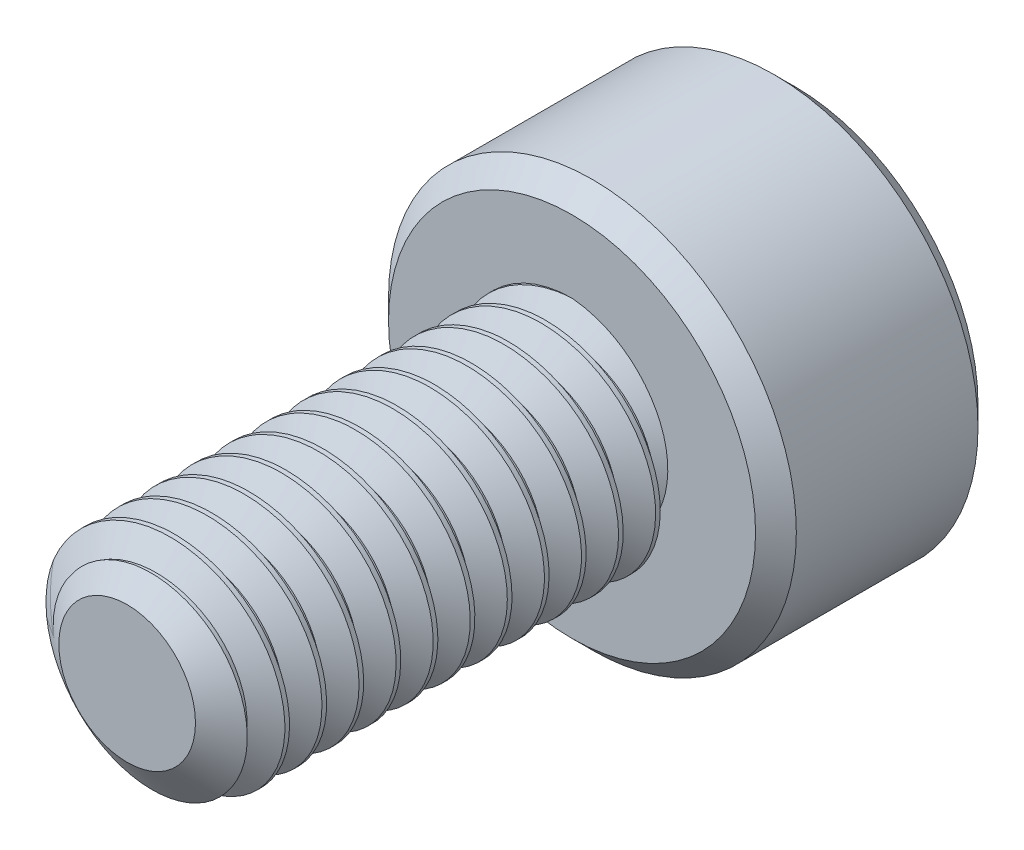
SolidWorks part; units mm, degrees
other "DetailItem1"
ref_plane "Front Plane" through (0, 0, 0) normal (0, 0, 1) x (1, 0, 0)
ref_plane "Top Plane" through (0, 0, 0) normal (0, 1, 0) x (1, 0, 0)
ref_plane "Right Plane" through (0, 0, 0) normal (1, 0, 0) x (0, 0, -1)
sketch "Sketch1" plane through (0, 0, 0) normal (0, 0, 1) x (1, 0, 0)
  circle A0 centre (0, 0) radius 1.5
  dimension "OD" = 3
extrude "Extrude1" add sketch "Sketch1" against normal blind 6
sketch "Sketch2" plane through (0, 0, 0) normal (0, 0, 1) x (1, 0, 0)
  circle A0 centre (0, 0) radius 1.5 construction
  circle A1 centre (0, 0) radius 1.5
curve "Helix/Spiral1" pitch 0.5 height 6.5 radius 1.5 centre (0, 0, 0) axis (0, 0, -1) start towards (0, 1, 0) parameters "pitch"=0.5
sketch "Sketch3" plane through (0, 0, 0) normal (1, 0, 0) x (0, 0, -1)
  line L0 (-0.4375, 1.5) -> (-0.25, 1.1752)
  line L1 (-0.25, 1.1752) -> (-0.1875, 1.1752)
  line L2 (-0.1875, 1.1752) -> (0, 1.5)
  line L3 (-0.4375, 1.5) -> (0, 1.5)
  line L4 (-0.2187, 1.5) -> (-0.2188, 1.1752) construction
  line L5 (-0.3438, 1.3376) -> (-0.0938, 1.3376) construction
  line L6 (0, 1.5) -> (0, -1.5) construction
  dimension "D1" = 0.0625
  dimension "D2" = 0.25
  dimension "D3" = 60
sweep "Cut-Sweep1" cut profiles "Sketch3" path "Helix/Spiral1" align with end faces yes
sketch "Sketch4" plane through (0, 0, 0) normal (1, 0, 0) x (0, 0, -1)
  line L0 (0.4053, 1.5) -> (0, 0.9212)
  line L1 (0, 0.9212) -> (0, 1.5)
  line L2 (0.4053, 1.5) -> (0, 1.5)
  line L3 (-0.4375, 1.5) -> (0, 1.5) construction
  line L4 (0, 0) -> (7.0209, 0) construction
  dimension "D1" = 55
  dimension "D2" = 0.254
revolve "Cut-Revolve1" cut sketch "Sketch4" angle 360 about L4
sketch "Sketch6" plane through (0, 0, -6) normal (0, 0, -1) x (-1, 0, 0)
  circle A0 centre (0, 0) radius 2.75
  dimension "head dia" = 5.5
extrude "Extrude2" add sketch "Sketch6" along normal blind 3
sketch "Sketch7" plane through (0, 0, -9) normal (0, 0, -1) x (-1, 0, 0)
  line L1 (0, 1.4434) -> (-1.25, 0.7217)
  line L2 (-1.25, 0.7217) -> (-1.25, -0.7217)
  line L3 (-1.25, -0.7217) -> (0, -1.4434)
  line L4 (0, -1.4434) -> (1.25, -0.7217)
  line L5 (1.25, -0.7217) -> (1.25, 0.7217)
  line L6 (1.25, 0.7217) -> (0, 1.4434)
  circle A0 centre (0, 0) radius 1.25 construction
  dimension "hex dia" = 2.5
extrude "Cut-Extrude1" cut sketch "Sketch7" against normal blind 1.875
sketch "Sketch8" plane through (0, 0, -9) normal (0, 0, -1) x (-1, 0, 0)
  circle A0 centre (0, 0) radius 1.4434
extrude "Cut-Extrude2" cut sketch "Sketch8" against normal through all draft 45
chamfer "Chamfer1" distance 0.275 angle 45 2 edges at (-2.75, 0, -9) (-2.75, 0, -6)
sketch "Sketch10" plane through (0, 0, -6) normal (0, 0, 1) x (1, 0, 0)
  circle A1 centre (0, 0) radius 1.5
  circle A2 centre (0, 0) radius 1.5
  dimension "D1" = 0
ref_plane "Plane1" through (0, 0, 0) normal (0, 0, 1) x (1, 0, 0)
extrude "partial thread" [suppressed] add sketch "Sketch10" along normal up to surface (4 mm away) separate body
chamfer "Chamfer2" [suppressed] distance 0.06 angle 45
combine bodies "Combine1" [suppressed] operation type add bodies to combine 107 108
sketch "Sketch9" plane through (0, 0, 0) normal (1, 0, 0) x (0, 0, -1)
  line L0 (0, 1.5) -> (0, -1.5) construction
  line L1 (1.25, 1.5) -> (1.25, -1.5) construction
  dimension "D1" = 1.25
equation "\"D3@Helix/Spiral1\" = \"screw length@Extrude1\"+\"pitch@Helix/Spiral1\""
equation "\"D1@Sketch3\" = \"pitch@Helix/Spiral1\"*.125"
equation "\"D2@Sketch3\" = \"pitch@Helix/Spiral1\"*.5"
equation "\"D1@Cut-Extrude1\" = \"hex dia@Sketch7\"*.75"
equation "\"D1@Chamfer1\" = \"head dia@Sketch6\"*.05"
equation "\"D1@Sketch9\" = \"pitch@Helix/Spiral1\"*2.5"
equation "\"D1@Chamfer2\"=\"OD@Sketch1\"*.02"
